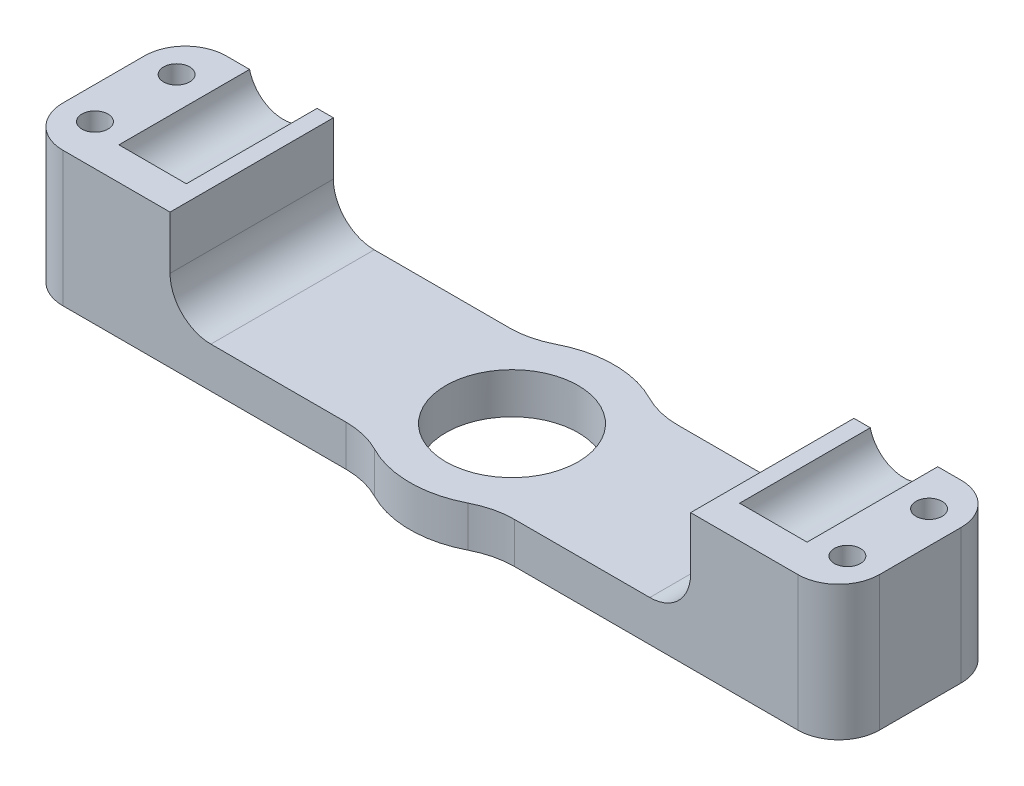
SolidWorks part; units mm, degrees
ref_plane "Front Plane" through (0, 0, 0) normal (0, 0, 1) x (1, 0, 0)
ref_plane "Top Plane" through (0, 0, 0) normal (0, 1, 0) x (1, 0, 0)
ref_plane "Right Plane" through (0, 0, 0) normal (1, 0, 0) x (0, 0, -1)
sketch "Sketch1" plane through (0, 0, 0) normal (0, 1, 0) x (1, 0, 0)
  line L0 (-44, 0) -> (-44, -44) construction
  line L1 (-44, -44) -> (44, -44) construction
  line L2 (44, -44) -> (44, 0) construction
  line L4 (-44, -10) -> (44, -10)
  line L5 (-44, -10) -> (-44, 10)
  line L6 (-44, 10) -> (44, 10)
  line L7 (44, -10) -> (44, 10)
  line L8 (-44, -10) -> (44, 10) construction
  line L9 (-44, 10) -> (44, -10) construction
  arc A0 (44, 0) -> (-44, 0) centre (0, 0) ccw construction
  dimension "D1" = 88
  dimension "D2" = 88
  dimension "D3" = 20
extrude "Boss-Extrude1" add sketch "Sketch1" along normal blind 35
sketch "Sketch2" plane through (0, 0, 10) normal (0, 0, 1) x (1, 0, 0)
  line L1 (-1044, 17.5) -> (48956, 17.5) construction
  line L2 (0, -1000) -> (0, 49000) construction
  line L3 (-44, 35) -> (-44, 0) construction
  circle A0 centre (-38, 17.5) radius 4.25
  circle A1 centre (38, 17.5) radius 4.25
  point P2 (-44, 17.5)
  dimension "D1" = 8.5
  dimension "D2" = 6
extrude "Cut-Extrude1" cut sketch "Sketch2" against normal through all
sketch "Sketch7" plane through (0, 35, 0) normal (0, 1, 0) x (1, 0, 0)
  circle A0 centre (0, 0) radius 12.5
  dimension "D1" = 25
extrude "Boss-Extrude2" add sketch "Sketch7" against normal up to surface (35 mm away) up to face at (0, 0, 0)
sketch "Sketch4" plane through (0, 35, 0) normal (0, 1, 0) x (1, 0, 0)
  circle A0 centre (0, 0) radius 8.1
  dimension "D1" = 16.2
extrude "Cut-Extrude3" cut sketch "Sketch4" against normal through all
fillet "Fillet2" radius 10 4 edges at (7.5, 17.5, 10) (-7.5, 17.5, 10) (7.5, 17.5, -10) (-7.5, 17.5, -10)
sketch "Sketch9" plane through (-44, 0, 0) normal (-1, 0, 0) x (0, 0, 1)
  line L5 (-1017.3065, 35) -> (48982.6935, 35) construction
  line L6 (-1016.9067, 16.5) -> (48983.0933, 16.5) construction
  line L7 (-12.5, 35) -> (-12.5, 0) construction
  line L8 (-10, 35) -> (10, 35) construction
  line L9 (12.5, 0) -> (12.5, 35) construction
  line L10 (-13.5, 35) -> (13.5, 35)
  line L11 (-13.5, 35) -> (-13.5, 16.5)
  line L12 (-13.5, 16.5) -> (13.5, 16.5)
  line L13 (13.5, 35) -> (13.5, 16.5)
  line L14 (-12.5, 35) -> (-12.5, 0) construction
  point P3 (-12.5, 16.5)
  point P16 (0, 0)
  point P21 (-12.5, 17.5)
  dimension "D1" = 1
  dimension "D2" = 1
  dimension "D3" = 1
extrude "Cut-Extrude4" cut sketch "Sketch9" against normal through all
sketch "Sketch10" plane through (0, 0, 0) normal (0, 0, 1) x (1, 0, 0)
  line L0 (44, 0) -> (10.3078, 0) construction
  line L1 (31.8693, 18.5) -> (-31.8693, 18.5)
  line L2 (31.8693, 18.5) -> (31.8693, 5)
  line L3 (31.8693, 5) -> (-31.8693, 5)
  line L4 (-31.8693, 18.5) -> (-31.8693, 5)
  line L5 (10.3078, 16.5) -> (33.8693, 16.5) construction
  dimension "D1" = 5
  dimension "D2" = 2
  dimension "D3" = 2
  dimension "D4" = 2
extrude "Cut-Extrude5" cut sketch "Sketch10" against normal through all and the other way through all
fillet "Fillet3" radius 5 2 edges at (-31.8693, 5, 0) (31.8693, 5, 0)
sketch "Sketch11" plane through (44, 0, 0) normal (1, 0, 0) x (0, 0, -1)
  line L4 (10, 0) -> (10, 16.5)
  line L5 (10, 16.5) -> (-10, 16.5)
  line L6 (-10, 16.5) -> (-10, 0)
  line L7 (-10, 0) -> (10, 0)
  line L8 (10, 0) -> (10, 16.5)
  line L9 (10, 16.5) -> (-10, 16.5)
  line L10 (-10, 16.5) -> (-10, 0)
  line L11 (-10, 0) -> (10, 0)
  dimension "D1" = 0
extrude "Boss-Extrude3" add sketch "Sketch11" along normal blind 6
sketch "Sketch12" plane through (0, 16.5, 0) normal (0, 1, 0) x (1, 0, 0)
  line L0 (50, -10) -> (42.1307, -10) construction
  line L1 (42.1307, 10) -> (50, 10) construction
  circle A0 centre (46.0653, 5) radius 1.6
  circle A1 centre (46.0653, -5) radius 1.6
  point P4 (46.0653, -10)
  point P5 (0, 0)
  dimension "D1" = 3.2
  dimension "D2" = 5
  dimension "D3" = 5
extrude "Cut-Extrude6" cut sketch "Sketch12" against normal through all
mirror "Mirror1" about plane through (0, 0, 0) normal (1, 0, 0) of "Cut-Extrude6", "Boss-Extrude3"
fillet "Fillet5" radius 5 4 edges at (-50, 8.25, -10) (-50, 8.25, 10) (50, 8.25, 10) (50, 8.25, -10)
sketch "Sketch13" plane through (0, 0, 10) normal (0, 0, 1) x (1, 0, 0)
  line L0 (-42.1307, 16.5) -> (-33.8693, 16.5)
  line L1 (33.8693, 16.5) -> (42.1307, 16.5)
  arc A0 (33.8693, 16.5) -> (42.1307, 16.5) centre (38, 17.5) ccw construction
  arc A1 (33.8693, 16.5) -> (42.1307, 16.5) centre (38, 17.5) ccw
  arc A2 (-42.1307, 16.5) -> (-33.8693, 16.5) centre (-38, 17.5) ccw construction
  arc A3 (-42.1307, 16.5) -> (-33.8693, 16.5) centre (-38, 17.5) ccw
extrude "Boss-Extrude4" add sketch "Sketch13" against normal blind 4
